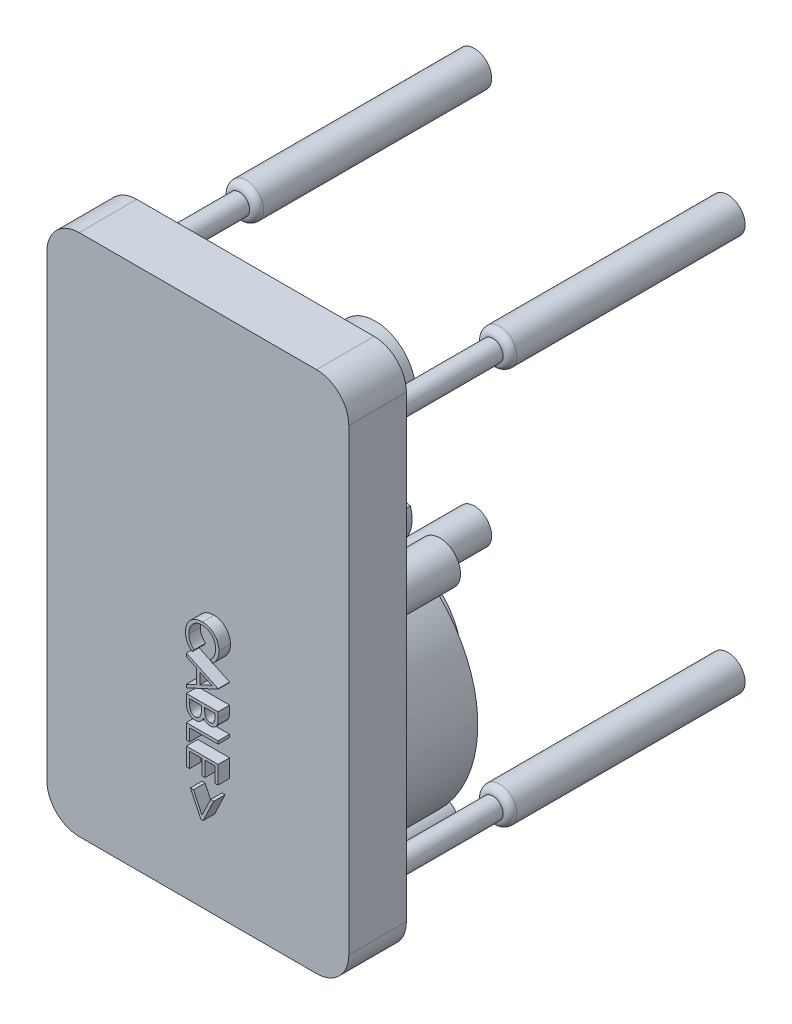
SolidWorks part; units mm, degrees
ref_plane "Front Plane" through (0, 0, 0) normal (0, 0, 1) x (1, 0, 0)
ref_plane "Top Plane" through (0, 0, 0) normal (0, 1, 0) x (1, 0, 0)
ref_plane "Right Plane" through (0, 0, 0) normal (1, 0, 0) x (0, 0, -1)
sketch "Sketch1" plane through (0, 0, 0) normal (0, 0, 1) x (1, 0, 0)
  line L0 (-13.081, 28.829) -> (13.081, 28.829)
  line L1 (-16.637, 25.273) -> (-16.637, -25.273)
  line L2 (-13.081, -28.829) -> (13.081, -28.829)
  line L3 (16.637, 25.273) -> (16.637, -25.273)
  line L4 (-16.637, 28.829) -> (16.637, -28.829) construction
  line L5 (-16.637, -28.829) -> (16.637, 28.829) construction
  line L6 (0, 36.9388) -> (0, -36.9388) construction
  line L7 (-21.0275, 0) -> (21.0275, 0) construction
  arc A0 (16.637, -25.273) -> (13.081, -28.829) centre (13.081, -25.273) cw
  arc A1 (-13.081, -28.829) -> (-16.637, -25.273) centre (-13.081, -25.273) cw
  arc A2 (16.637, 25.273) -> (13.081, 28.829) centre (13.081, 25.273) ccw
  arc A3 (-13.081, 28.829) -> (-16.637, 25.273) centre (-13.081, 25.273) ccw
  circle A4 centre (0, -12.7) radius 7.239
  circle A5 centre (0, 12.7) radius 4.445
  circle A6 centre (0, 14.605) radius 6.35
  circle A7 centre (0, -12.7) radius 14.351
  arc A8 (-3.6204, 1.1868) -> (3.6204, 1.1868) centre (0, 0) ccw
  circle A9 centre (13.97, 21.844) radius 1.016
  circle A10 centre (-13.97, 21.844) radius 1.016
  circle A11 centre (13.97, -21.844) radius 1.016
  circle A12 centre (-13.97, -21.844) radius 1.016
  arc A13 (6.6635, 0.0102) -> (10.0641, -2.4694) centre (8.89, -0.508) cw
  arc A14 (-10.0641, -2.4694) -> (-6.6635, 0.0102) centre (-8.89, -0.508) cw
  arc A15 (-10.0641, -22.9306) -> (-6.6635, -25.4102) centre (-8.89, -24.892) ccw
  arc A16 (6.6635, -25.4102) -> (10.0641, -22.9306) centre (8.89, -24.892) ccw
  point P0 (0, 0)
  dimension "D3" = 3.556
  dimension "D4" = 14.478
  dimension "D5" = 8.89
  dimension "D6" = 12.7
  dimension "D8" = 7.62
  dimension "D10" = 2.032
  dimension "D12" = 28.702
  dimension "D13" = 2.286
  dimension "D1" = 33.274
  dimension "D2" = 57.658
  dimension "D7" = 12.7
  dimension "D9" = 21.844
  dimension "D11" = 13.97
  dimension "D14" = 8.89
  dimension "D15" = 0.508
  dimension "D16" = 0.508
  dimension "D17" = 8.89
  dimension "D18" = 24.892
  dimension "D19" = 24.892
  dimension "D20" = 8.89
  dimension "D21" = 8.89
extrude "Boss-Extrude1" add sketch "Sketch1" against normal blind 10.16 contours A8 A7 A4 | A14 A7 | A7 A8 | A13 A7 | A7 A16 | A7 A15 | A4 region at (0, -12.7, 0) region at (12.8646, -18.0906, 0) region at (9.2197, -0.0559, 0) region at (9.2197, -25.3441, 0) region at (0, -0.8411, 0) region at (-9.2197, -25.3441, 0) region at (-9.2197, -0.0559, 0)
sketch "Sketch2" plane through (0, 0, 0) normal (0, 0, 1) x (1, 0, 0)
  line L0 (-13.081, 28.829) -> (13.081, 28.829)
  line L1 (-16.637, 25.273) -> (-16.637, -25.273)
  line L2 (-13.081, -28.829) -> (13.081, -28.829)
  line L3 (16.637, 25.273) -> (16.637, -25.273)
  line L4 (-16.637, 28.829) -> (16.637, -28.829) construction
  line L5 (-16.637, -28.829) -> (16.637, 28.829) construction
  line L6 (0, 38.9705) -> (0, -34.9071) construction
  line L7 (-9.8575, 0) -> (32.1974, 0) construction
  arc A0 (16.637, -25.273) -> (13.081, -28.829) centre (13.081, -25.273) cw
  arc A1 (-13.081, -28.829) -> (-16.637, -25.273) centre (-13.081, -25.273) cw
  arc A2 (16.637, 25.273) -> (13.081, 28.829) centre (13.081, 25.273) ccw
  arc A3 (-13.081, 28.829) -> (-16.637, 25.273) centre (-13.081, 25.273) ccw
  circle A4 centre (0, -12.7) radius 7.239
  circle A5 centre (0, 12.7) radius 4.445
  circle A6 centre (0, 14.605) radius 6.35
  circle A7 centre (0, -12.7) radius 14.351
  arc A8 (-3.6204, 1.1868) -> (3.6204, 1.1868) centre (0, 0) ccw
  circle A9 centre (13.97, 21.844) radius 1.016
  circle A10 centre (-13.97, 21.844) radius 1.016
  circle A11 centre (13.97, -21.844) radius 1.016
  circle A12 centre (-13.97, -21.844) radius 1.016
  arc A13 (6.6635, 0.0102) -> (10.0641, -2.4694) centre (8.89, -0.508) cw
  arc A14 (-10.0641, -2.4694) -> (-6.6635, 0.0102) centre (-8.89, -0.508) cw
  arc A15 (-10.0641, -22.9306) -> (-6.6635, -25.4102) centre (-8.89, -24.892) ccw
  arc A16 (6.6635, -25.4102) -> (10.0641, -22.9306) centre (8.89, -24.892) ccw
  point P0 (0, 0)
  dimension "D3" = 3.556
  dimension "D4" = 14.478
  dimension "D5" = 8.89
  dimension "D6" = 12.7
  dimension "D8" = 7.62
  dimension "D10" = 2.032
  dimension "D12" = 28.702
  dimension "D13" = 2.286
  dimension "D1" = 33.274
  dimension "D2" = 57.658
  dimension "D7" = 12.7
  dimension "D9" = 21.844
  dimension "D11" = 13.97
  dimension "D14" = 8.89
  dimension "D15" = 0.508
  dimension "D16" = 0.508
  dimension "D17" = 8.89
  dimension "D18" = 24.892
  dimension "D19" = 24.892
  dimension "D20" = 8.89
  dimension "D21" = 8.89
extrude "Boss-Extrude2" add sketch "Sketch2" against normal blind 1.778 separate body contours A5 | A5 A6 region at (0, 12.7, 0) region at (-4.3631, 18.9681, 0)
sketch "Sketch3" plane through (0, 0, -10.16) normal (0, 0, -1) x (-1, 0, 0)
  circle A0 centre (-8.89, -0.508) radius 2.286
  circle A1 centre (8.89, -24.892) radius 2.286
  circle A2 centre (-8.89, -24.892) radius 2.286
  circle A3 centre (8.89, -0.508) radius 2.286
extrude "Boss-Extrude3" add sketch "Sketch3" along normal blind 1.27
sketch "Sketch4" plane through (0, 0, -10.16) normal (0, 0, -1) x (-1, 0, 0)
  line L0 (-13.081, 28.829) -> (13.081, 28.829)
  line L1 (-16.637, 25.273) -> (-16.637, -25.273)
  line L2 (-13.081, -28.829) -> (13.081, -28.829)
  line L3 (16.637, 25.273) -> (16.637, -25.273)
  line L4 (-16.637, 28.829) -> (16.637, -28.829) construction
  line L5 (-16.637, -28.829) -> (16.637, 28.829) construction
  line L6 (0, 23.9866) -> (0, -49.891) construction
  line L7 (7.1619, 0) -> (49.2169, 0) construction
  arc A0 (16.637, -25.273) -> (13.081, -28.829) centre (13.081, -25.273) cw
  arc A1 (-13.081, -28.829) -> (-16.637, -25.273) centre (-13.081, -25.273) cw
  arc A2 (16.637, 25.273) -> (13.081, 28.829) centre (13.081, 25.273) ccw
  arc A3 (-13.081, 28.829) -> (-16.637, 25.273) centre (-13.081, 25.273) ccw
  circle A4 centre (0, -12.7) radius 7.239
  circle A5 centre (0, 12.7) radius 4.445
  circle A6 centre (0, 14.605) radius 6.35
  circle A7 centre (0, -12.7) radius 14.351
  arc A8 (-3.6204, 1.1868) -> (3.6204, 1.1868) centre (0, 0) ccw
  circle A9 centre (13.97, 21.844) radius 1.016
  circle A10 centre (-13.97, 21.844) radius 1.016
  circle A11 centre (13.97, -21.844) radius 1.016
  circle A12 centre (-13.97, -21.844) radius 1.016
  arc A13 (6.6635, 0.0102) -> (10.0641, -2.4694) centre (8.89, -0.508) cw
  arc A14 (-10.0641, -2.4694) -> (-6.6635, 0.0102) centre (-8.89, -0.508) cw
  arc A15 (-10.0641, -22.9306) -> (-6.6635, -25.4102) centre (-8.89, -24.892) ccw
  arc A16 (6.6635, -25.4102) -> (10.0641, -22.9306) centre (8.89, -24.892) ccw
  point P0 (0, 0)
  dimension "D3" = 3.556
  dimension "D4" = 14.478
  dimension "D5" = 8.89
  dimension "D6" = 12.7
  dimension "D8" = 7.62
  dimension "D10" = 2.032
  dimension "D12" = 28.702
  dimension "D13" = 2.286
  dimension "D1" = 33.274
  dimension "D2" = 57.658
  dimension "D7" = 12.7
  dimension "D9" = 21.844
  dimension "D11" = 13.97
  dimension "D14" = 8.89
  dimension "D15" = 0.508
  dimension "D16" = 0.508
  dimension "D17" = 8.89
  dimension "D18" = 24.892
  dimension "D19" = 24.892
  dimension "D20" = 8.89
  dimension "D21" = 8.89
extrude "Boss-Extrude4" add sketch "Sketch4" along normal blind 3.302 contours A7 A8 region at (0, -0.8411, -10.16)
sketch "Sketch5" plane through (0, 0, -1.778) normal (0, 0, -1) x (-1, 0, 0)
  line L0 (-13.081, 28.829) -> (13.081, 28.829)
  line L1 (-16.637, 25.273) -> (-16.637, -25.273)
  line L2 (-13.081, -28.829) -> (13.081, -28.829)
  line L3 (16.637, 25.273) -> (16.637, -25.273)
  line L4 (-16.637, 28.829) -> (16.637, -28.829) construction
  line L5 (-16.637, -28.829) -> (16.637, 28.829) construction
  line L6 (0, 36.0331) -> (0, -37.8445) construction
  line L7 (26.8703, 0) -> (68.9252, 0) construction
  arc A0 (16.637, -25.273) -> (13.081, -28.829) centre (13.081, -25.273) cw
  arc A1 (-13.081, -28.829) -> (-16.637, -25.273) centre (-13.081, -25.273) cw
  arc A2 (16.637, 25.273) -> (13.081, 28.829) centre (13.081, 25.273) ccw
  arc A3 (-13.081, 28.829) -> (-16.637, 25.273) centre (-13.081, 25.273) ccw
  circle A4 centre (0, -12.7) radius 7.239
  circle A5 centre (0, 12.7) radius 4.445
  circle A6 centre (0, 14.605) radius 6.35
  circle A7 centre (0, -12.7) radius 14.351
  arc A8 (-3.6204, 1.1868) -> (3.6204, 1.1868) centre (0, 0) ccw
  circle A9 centre (13.97, 21.844) radius 1.016
  circle A10 centre (-13.97, 21.844) radius 1.016
  circle A11 centre (13.97, -21.844) radius 1.016
  circle A12 centre (-13.97, -21.844) radius 1.016
  arc A13 (6.6635, 0.0102) -> (10.0641, -2.4694) centre (8.89, -0.508) cw
  arc A14 (-10.0641, -2.4694) -> (-6.6635, 0.0102) centre (-8.89, -0.508) cw
  arc A15 (-10.0641, -22.9306) -> (-6.6635, -25.4102) centre (-8.89, -24.892) ccw
  arc A16 (6.6635, -25.4102) -> (10.0641, -22.9306) centre (8.89, -24.892) ccw
  point P0 (0, 0)
  dimension "D3" = 3.556
  dimension "D4" = 14.478
  dimension "D5" = 8.89
  dimension "D6" = 12.7
  dimension "D8" = 7.62
  dimension "D10" = 2.032
  dimension "D12" = 28.702
  dimension "D13" = 2.286
  dimension "D1" = 33.274
  dimension "D2" = 57.658
  dimension "D7" = 12.7
  dimension "D9" = 21.844
  dimension "D11" = 13.97
  dimension "D14" = 8.89
  dimension "D15" = 0.508
  dimension "D16" = 0.508
  dimension "D17" = 8.89
  dimension "D18" = 24.892
  dimension "D19" = 24.892
  dimension "D20" = 8.89
  dimension "D21" = 8.89
extrude "Boss-Extrude5" add sketch "Sketch5" along normal blind 11.43 contours A5 region at (0, 12.7, -1.778)
sketch "Sketch6" plane through (0, 0, 0) normal (0, 0, 1) x (1, 0, 0)
  line L0 (-13.081, 28.829) -> (13.081, 28.829)
  line L1 (-16.637, 25.273) -> (-16.637, -25.273)
  line L2 (-13.081, -28.829) -> (13.081, -28.829)
  line L3 (16.637, 25.273) -> (16.637, -25.273)
  line L4 (-16.637, 28.829) -> (16.637, -28.829) construction
  line L5 (-16.637, -28.829) -> (16.637, 28.829) construction
  line L6 (0, 36.0885) -> (0, -37.789) construction
  line L7 (-47.9194, 0) -> (-5.8644, 0) construction
  arc A0 (16.637, -25.273) -> (13.081, -28.829) centre (13.081, -25.273) cw
  arc A1 (-13.081, -28.829) -> (-16.637, -25.273) centre (-13.081, -25.273) cw
  arc A2 (16.637, 25.273) -> (13.081, 28.829) centre (13.081, 25.273) ccw
  arc A3 (-13.081, 28.829) -> (-16.637, 25.273) centre (-13.081, 25.273) ccw
  circle A4 centre (0, -12.7) radius 7.239
  circle A5 centre (0, 12.7) radius 4.445
  circle A6 centre (0, 14.605) radius 6.35
  circle A7 centre (0, -12.7) radius 14.351
  arc A8 (-3.6204, 1.1868) -> (3.6204, 1.1868) centre (0, 0) ccw
  circle A9 centre (13.97, 21.844) radius 1.143
  circle A10 centre (-13.97, 21.844) radius 1.143
  circle A11 centre (13.97, -21.844) radius 1.143
  circle A12 centre (-13.97, -21.844) radius 1.143
  arc A13 (6.6635, 0.0102) -> (10.0641, -2.4694) centre (8.89, -0.508) cw
  arc A14 (-10.0641, -2.4694) -> (-6.6635, 0.0102) centre (-8.89, -0.508) cw
  arc A15 (-10.0641, -22.9306) -> (-6.6635, -25.4102) centre (-8.89, -24.892) ccw
  arc A16 (6.6635, -25.4102) -> (10.0641, -22.9306) centre (8.89, -24.892) ccw
  point P0 (0, 0)
  dimension "D3" = 3.556
  dimension "D4" = 14.478
  dimension "D5" = 8.89
  dimension "D6" = 12.7
  dimension "D8" = 7.62
  dimension "D10" = 2.286
  dimension "D12" = 28.702
  dimension "D13" = 2.286
  dimension "D1" = 33.274
  dimension "D2" = 57.658
  dimension "D7" = 12.7
  dimension "D9" = 21.844
  dimension "D11" = 13.97
  dimension "D14" = 8.89
  dimension "D15" = 0.508
  dimension "D16" = 0.508
  dimension "D17" = 8.89
  dimension "D18" = 24.892
  dimension "D19" = 24.892
  dimension "D20" = 8.89
  dimension "D21" = 8.89
extrude "Boss-Extrude6" add sketch "Sketch6" against normal blind 38.1 separate body contours A10 | A9 | A12 | A11 region at (13.97, 21.844, 0) region at (-13.97, 21.844, 0) region at (13.97, -21.844, 0) region at (-13.97, -21.844, 0)
sketch "Sketch7" plane through (0, 0, -10.16) normal (0, 0, -1) x (-1, 0, 0)
  line L0 (-13.081, 28.829) -> (13.081, 28.829)
  line L1 (-16.637, 25.273) -> (-16.637, -25.273)
  line L2 (-13.081, -28.829) -> (13.081, -28.829)
  line L3 (16.637, 25.273) -> (16.637, -25.273)
  line L4 (-16.637, 28.829) -> (16.637, -28.829) construction
  line L5 (-16.637, -28.829) -> (16.637, 28.829) construction
  line L6 (0, 26.9541) -> (0, -46.9235) construction
  line L7 (8.0915, 0) -> (50.1464, 0) construction
  arc A0 (16.637, -25.273) -> (13.081, -28.829) centre (13.081, -25.273) cw
  arc A1 (-13.081, -28.829) -> (-16.637, -25.273) centre (-13.081, -25.273) cw
  arc A2 (16.637, 25.273) -> (13.081, 28.829) centre (13.081, 25.273) ccw
  arc A3 (-13.081, 28.829) -> (-16.637, 25.273) centre (-13.081, 25.273) ccw
  circle A4 centre (0, -12.7) radius 7.239
  circle A5 centre (0, 12.7) radius 4.445
  circle A6 centre (0, 14.605) radius 6.35
  circle A7 centre (0, -12.7) radius 14.351
  arc A8 (-3.6204, 1.1868) -> (3.6204, 1.1868) centre (0, 0) ccw
  circle A9 centre (13.97, 21.844) radius 1.016
  circle A10 centre (-13.97, 21.844) radius 1.016
  circle A11 centre (13.97, -21.844) radius 1.016
  circle A12 centre (-13.97, -21.844) radius 1.016
  arc A13 (6.6635, 0.0102) -> (10.0641, -2.4694) centre (8.89, -0.508) cw
  arc A14 (-10.0641, -2.4694) -> (-6.6635, 0.0102) centre (-8.89, -0.508) cw
  arc A15 (-10.0641, -22.9306) -> (-6.6635, -25.4102) centre (-8.89, -24.892) ccw
  arc A16 (6.6635, -25.4102) -> (10.0641, -22.9306) centre (8.89, -24.892) ccw
  point P0 (0, 0)
  dimension "D3" = 3.556
  dimension "D4" = 14.478
  dimension "D5" = 8.89
  dimension "D6" = 12.7
  dimension "D8" = 7.62
  dimension "D10" = 2.032
  dimension "D12" = 28.702
  dimension "D13" = 2.286
  dimension "D1" = 33.274
  dimension "D2" = 57.658
  dimension "D7" = 12.7
  dimension "D9" = 21.844
  dimension "D11" = 13.97
  dimension "D14" = 8.89
  dimension "D15" = 0.508
  dimension "D16" = 0.508
  dimension "D17" = 8.89
  dimension "D18" = 24.892
  dimension "D19" = 24.892
  dimension "D20" = 8.89
  dimension "D21" = 8.89
extrude "Boss-Extrude7" add sketch "Sketch7" along normal blind 5.334 contours A4 region at (0, -12.7, -10.16)
sketch "Sketch8" plane through (0, 0, 0) normal (0, 0, 1) x (1, 0, 0)
  line L1 (-13.081, 28.829) -> (13.081, 28.829)
  line L2 (-16.637, 25.273) -> (-16.637, -25.273)
  line L3 (-13.081, -28.829) -> (13.081, -28.829)
  line L4 (16.637, 25.273) -> (16.637, -25.273)
  line L5 (-16.637, 28.829) -> (16.637, -28.829) construction
  line L6 (-16.637, -28.829) -> (16.637, 28.829) construction
  arc A8 (16.637, -25.273) -> (13.081, -28.829) centre (13.081, -25.273) cw
  arc A13 (-13.081, -28.829) -> (-16.637, -25.273) centre (-13.081, -25.273) cw
  arc A14 (16.637, 25.273) -> (13.081, 28.829) centre (13.081, 25.273) ccw
  arc A15 (-13.081, 28.829) -> (-16.637, 25.273) centre (-13.081, 25.273) ccw
  point P0 (0, 0)
  dimension "D3" = 3.556
  dimension "D1" = 33.274
  dimension "D23" = 57.658
extrude "Boss-Extrude8" add sketch "Sketch8" along normal blind 6.35
sketch "Sketch9" plane through (0, 0, -38.1) normal (0, 0, -1) x (-1, 0, 0)
  circle A0 centre (-13.97, 21.844) radius 1.905
  circle A1 centre (13.97, 21.844) radius 1.905
  circle A2 centre (13.97, -21.844) radius 1.905
  circle A3 centre (-13.97, -21.844) radius 1.905
  dimension "D1" = 3.81
extrude "Boss-Extrude9" add sketch "Sketch9" against normal offset from surface (25.908 mm away) 12.192 up to face at (12.827, -21.844, 0)
sketch "Sketch10" plane through (0, 0, 6.35) normal (0, 0, 1) x (1, 0, 0)
  line L0 (0, 0) -> (0, -28.829) construction
  line L1 (-13.081, -28.829) -> (13.081, -28.829) construction
  text T0 "CABLE >"
extrude "Boss-Extrude10" add sketch "Sketch10" along normal blind 1.27
fillet "Fillet1" radius 0.762 4 edges at (-15.875, 21.844, -12.192) (12.065, 21.844, -12.192) (-15.875, -21.844, -12.192) (12.065, -21.844, -12.192)
